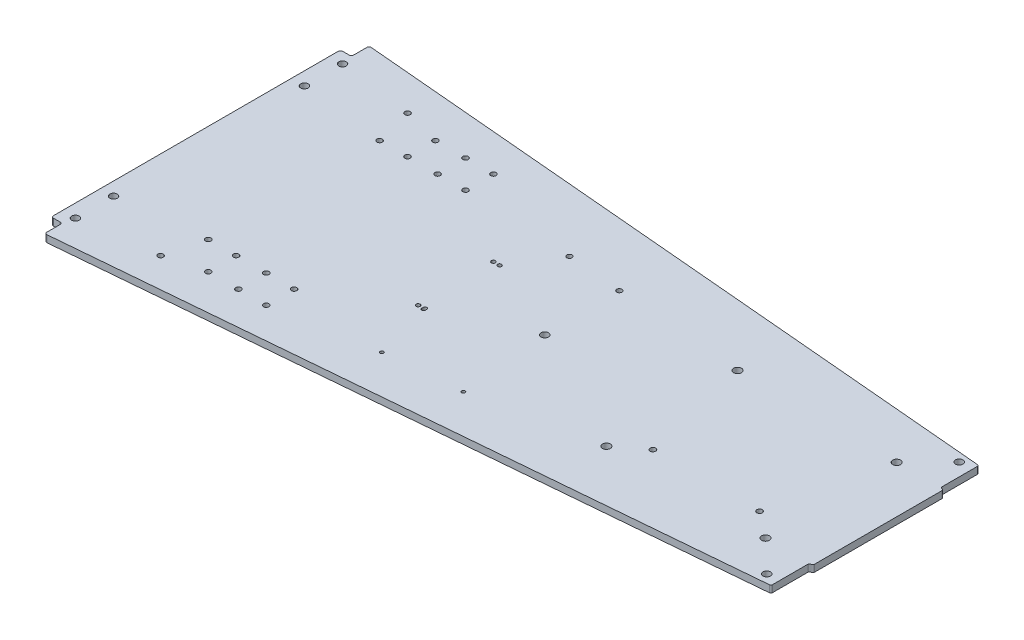
SolidWorks part; units mm, degrees
ref_plane "Front Plane" through (0, 0, 0) normal (0, 0, 1) x (1, 0, 0)
ref_plane "Top Plane" through (0, 0, 0) normal (0, 1, 0) x (1, 0, 0)
ref_plane "Right Plane" through (0, 0, 0) normal (1, 0, 0) x (0, 0, -1)
sketch "Sketch1" plane through (0, 0, 0) normal (0, 1, 0) x (1, 0, 0)
  line L0 (0, -94.3735) -> (0, 94.3735)
  line L1 (0, 94.3735) -> (-621.5262, 148.75)
  line L2 (-621.5262, 148.75) -> (-621.5262, -148.75)
  line L3 (-621.5262, -148.75) -> (0, -94.3735)
  point P7 (0, 0)
  dimension "D1" = 188.747
  dimension "D2" = 297.5
  dimension "D3" = 95
  dimension "D4" = 95
extrude "Boss-Extrude1" add sketch "Sketch1" along normal mid plane 6.35
hole_wizard "M3 Clearance Hole1" positions "Sketch8" profile "Sketch9" hole size "M3" standard "ANSI Metric" end condition through all
sketch "Sketch8" plane through (0, 3.175, 0) normal (0, 1, 0) x (1, 0, 0)
  point P0 (-379.222, 34.29)
  point P3 (-384.81, 34.29)
  point P6 (-384.81, -34.29)
sketch "Sketch9" plane through (-379.222, 3.175, -34.29) normal (1, 0, 0) x (0, 0, 1)
  line L0 (0, 0) -> (0, 6.35)
  line L1 (0, 6.35) -> (1.8, 6.35)
  line L2 (1.8, 6.35) -> (1.8, 0)
  line L5 (1.8, 0) -> (0, 0)
  line L11 (0, -6.35) -> (0, 107.95) construction
  dimension "Thru Hole Dia." = 3.6
  dimension "Thru Hole Depth" = 6.35
hole_wizard "1/4 Clearance Hole1" positions "Sketch10" profile "Sketch11" hole size "1/4" standard "ANSI Inch" end condition through all
sketch "Sketch10" plane through (0, 3.175, 0) normal (0, 1, 0) x (1, 0, 0)
  point P0 (-187.8373, 59.7527)
  point P3 (-42.9319, 59.7527)
  point P6 (-42.9319, -59.7527)
  point P9 (-187.8373, -59.7527)
sketch "Sketch11" plane through (-187.8373, 3.175, -59.7527) normal (1, 0, 0) x (0, 0, 1)
  line L0 (0, 0) -> (0, 6.35)
  line L1 (0, 6.35) -> (3.5712, 6.35)
  line L2 (3.5712, 6.35) -> (3.5712, 0)
  line L5 (3.5712, 0) -> (0, 0)
  line L11 (0, -6.35) -> (0, 107.95) construction
  dimension "Thru Hole Dia." = 7.1425
  dimension "Thru Hole Depth" = 6.35
sketch "Sketch12" plane through (0, 3.175, 0) normal (0, 1, 0) x (1, 0, 0)
  line L0 (-380.8412, -33.6169) -> (-380.8412, -34.0868) construction
  line L1 (-380.8412, -34.4932) -> (-380.8412, -34.9631) construction
  line L2 (-377.6027, -34.9631) -> (-377.6027, -34.4932) construction
  line L3 (-377.6027, -34.0868) -> (-377.6027, -33.6169) construction
  line L4 (-380.8412, -33.6169) -> (-380.8412, -34.0868)
  line L5 (-380.8412, -34.4932) -> (-380.8412, -34.9631)
  line L6 (-377.6027, -34.9631) -> (-377.6027, -34.4932)
  line L7 (-377.6027, -34.0868) -> (-377.6027, -33.6169)
  arc A0 (-380.8412, -34.0868) -> (-380.8412, -34.4932) centre (-379.222, -34.29) ccw construction
  arc A1 (-380.8412, -34.9631) -> (-377.6027, -34.9631) centre (-379.222, -34.9631) ccw construction
  arc A2 (-377.6027, -34.4932) -> (-377.6027, -34.0868) centre (-379.222, -34.29) ccw construction
  arc A3 (-377.6027, -33.6169) -> (-380.8412, -33.6169) centre (-379.222, -33.6169) ccw construction
  arc A4 (-380.8412, -34.0868) -> (-380.8412, -34.4932) centre (-379.222, -34.29) ccw
  arc A5 (-380.8412, -34.9631) -> (-377.6027, -34.9631) centre (-379.222, -34.9631) ccw
  arc A6 (-377.6027, -34.4932) -> (-377.6027, -34.0868) centre (-379.222, -34.29) ccw
  arc A7 (-377.6027, -33.6169) -> (-380.8412, -33.6169) centre (-379.222, -33.6169) ccw
extrude "Cut-Extrude1" cut sketch "Sketch12" against normal through all
hole_wizard "#8 Clearance Hole1" positions "Sketch13" profile "Sketch14" hole size "#8" standard "ANSI Inch" end condition through all
sketch "Sketch13" plane through (0, 3.175, 0) normal (0, 1, 0) x (1, 0, 0)
  point P0 (-506.818, -78.0643)
  point P3 (-506.818, -103.4643)
  point P6 (-541.1982, -112.4445)
  point P9 (-532.218, -78.0643)
  point P12 (-479.3927, -78.0643)
  point P15 (-479.3927, -103.4643)
  point P18 (-453.9927, -78.0643)
  point P21 (-453.9927, -103.4643)
  point P24 (-453.9927, 78.0643)
  point P27 (-453.9927, 103.4643)
  point P30 (-479.3927, 78.0643)
  point P33 (-479.3927, 103.4643)
  point P36 (-541.1982, 112.4445)
  point P39 (-532.218, 78.0643)
  point P42 (-506.818, 103.4643)
  point P45 (-506.818, 78.0643)
sketch "Sketch14" plane through (-506.818, 3.175, 78.0643) normal (1, 0, 0) x (0, 0, 1)
  line L0 (0, 0) -> (0, 6.35)
  line L1 (0, 6.35) -> (2.4574, 6.35)
  line L2 (2.4574, 6.35) -> (2.4574, 0)
  line L5 (2.4574, 0) -> (0, 0)
  line L11 (0, -6.35) -> (0, 107.95) construction
  dimension "Thru Hole Dia." = 4.9149
  dimension "Thru Hole Depth" = 6.35
sketch "Sketch15" plane through (0, 3.175, 0) normal (0, 1, 0) x (1, 0, 0)
  circle A0 centre (-295.9182, -81.917) radius 1.55 construction
  circle A1 centre (-364.1575, -87.8871) radius 1.55 construction
  circle A6 centre (-295.9182, -81.917) radius 1.55
  circle A7 centre (-364.1575, -87.8871) radius 1.55
extrude "Cut-Extrude2" cut sketch "Sketch15" against normal through all
sketch "Sketch16" plane through (0, 3.175, 0) normal (0, 1, 0) x (1, 0, 0)
  circle A0 centre (-609.6, -121.6503) radius 3.3782 construction
  circle A1 centre (-609.6, -86.9431) radius 3.3782 construction
  circle A2 centre (-609.6, 86.9431) radius 3.3782 construction
  circle A3 centre (-609.6, 121.6503) radius 3.3782 construction
  circle A4 centre (-609.6, -121.6503) radius 3.3782
  circle A5 centre (-609.6, -86.9431) radius 3.3782
  circle A6 centre (-609.6, 86.9431) radius 3.3782
  circle A7 centre (-609.6, 121.6503) radius 3.3782
extrude "Cut-Extrude3" cut sketch "Sketch16" against normal through all
fillet "Fillet1" radius 1 2 edges at (-621.5262, 0, 148.75) (-621.5262, 0, -148.75)
sketch "Sketch17" plane through (0, 3.175, 0) normal (0, 1, 0) x (1, 0, 0)
  line L0 (-3, 94.636) -> (-3, 59.636)
  line L1 (0, 94.3735) -> (-620.4391, 148.6549) construction
  line L2 (-3, 59.636) -> (0, 59.636)
  line L3 (0, -94.3735) -> (0, 94.3735) construction
  line L4 (0, 59.636) -> (0, 94.3735)
  line L5 (0, 94.3735) -> (-3, 94.636)
  dimension "D1" = 3
  dimension "D2" = 35
extrude "Cut-Extrude4" cut sketch "Sketch17" against normal through all
mirror "Mirror1" about plane through (0, 0, 0) normal (0, 0, 1) of "Cut-Extrude4"
fillet "Fillet2" radius 1.5 6 edges at (0, 0, -59.636) (-3, 0, -59.636) (-3, 0, -94.636) (0, 0, 59.636) (-3, 0, 59.636) (-3, 0, 94.636)
hole_wizard "#13 (0.185) Diameter Hole1" positions "Sketch18" profile "Sketch20" hole size "#13" standard "ANSI Inch" end condition through all
sketch "Sketch18" plane through (0, 3.175, 0) normal (0, 1, 0) x (1, 0, 0)
  point P0 (-354.4456, 73.1877)
  point P3 (-304.6358, 68.83)
sketch "Sketch20" plane through (-354.4456, 3.175, -73.1877) normal (1, 0, 0) x (0, 0, 1)
  line L0 (0, 0) -> (0, 6.35)
  line L1 (0, 6.35) -> (2.3495, 6.35)
  line L2 (2.3495, 6.35) -> (2.3495, 0)
  line L5 (2.3495, 0) -> (0, 0)
  line L11 (0, -6.35) -> (0, 107.95) construction
  dimension "Thru Hole Dia." = 4.699
  dimension "Thru Hole Depth" = 6.35
hole_wizard "1/4 Clearance Hole2" positions "Sketch21" profile "Sketch22" hole size "1/4" standard "ANSI Inch" end condition through all
sketch "Sketch21" plane through (0, 3.175, 0) normal (0, 1, 0) x (1, 0, 0)
  point P0 (-14.732, 88.4699)
  point P3 (-14.0462, -87.4539)
  point P6 (-303.7332, 0)
sketch "Sketch22" plane through (-14.732, 3.175, -88.4699) normal (1, 0, 0) x (0, 0, 1)
  line L0 (0, 0) -> (0, 6.35)
  line L1 (0, 6.35) -> (3.3782, 6.35)
  line L2 (3.3782, 6.35) -> (3.3782, 0)
  line L5 (3.3782, 0) -> (0, 0)
  line L11 (0, -6.35) -> (0, 107.95) construction
  dimension "Thru Hole Dia." = 6.7564
  dimension "Thru Hole Depth" = 6.35
sketch "Sketch23" plane through (0, 3.175, 0) normal (0, 1, 0) x (1, 0, 0)
  line L0 (-621.5262, 147.6587) -> (-621.5262, -147.6587) construction
  line L1 (-621.5262, 131.6587) -> (-611.5262, 131.6587)
  line L2 (-621.5262, 131.6587) -> (-621.5262, 148.6587)
  line L3 (-621.5262, 148.6587) -> (-611.5262, 148.6587)
  line L4 (-611.5262, 131.6587) -> (-611.5262, 148.6587)
  line L5 (0, 0) -> (-621.5262, 0) construction
  line L6 (-611.5262, -131.6587) -> (-611.5262, -148.6587)
  line L7 (-621.5262, -148.6587) -> (-611.5262, -148.6587)
  line L8 (-621.5262, -131.6587) -> (-621.5262, -148.6587)
  line L9 (-621.5262, -131.6587) -> (-611.5262, -131.6587)
  arc A0 (-620.4391, 148.6549) -> (-621.5262, 147.6587) centre (-620.5262, 147.6587) ccw construction
  dimension "D1" = 10
  dimension "D2" = 17
extrude "Cut-Extrude5" cut sketch "Sketch23" against normal through all
fillet "Fillet3" radius 2 6 edges at (-621.5262, 0, -131.6587) (-611.5262, 0, -131.6587) (-611.5262, 0, -147.8751) (-611.5262, 0, 147.8751) (-611.5262, 0, 131.6587) (-621.5262, 0, 131.6587)
hole_wizard "Ø5.0mm Dowel Hole1" positions "Sketch24" profile "Sketch25" hole size "Ø5.0" standard "ANSI Metric" end condition through all
sketch "Sketch24" plane through (0, 3.175, 0) normal (0, 1, 0) x (1, 0, 0)
  point P0 (-163.9621, -41.275)
  point P3 (-66.8071, -41.275)
sketch "Sketch25" plane through (-163.9621, 3.175, 41.275) normal (1, 0, 0) x (0, 0, 1)
  line L0 (0, 0) -> (0, 6.35)
  line L1 (0, 6.35) -> (2.5, 6.35)
  line L2 (2.5, 6.35) -> (2.5, 0)
  line L5 (2.5, 0) -> (0, 0)
  line L11 (0, -6.35) -> (0, 107.95) construction
  dimension "Thru Hole Dia." = 5
  dimension "Thru Hole Depth" = 6.35
